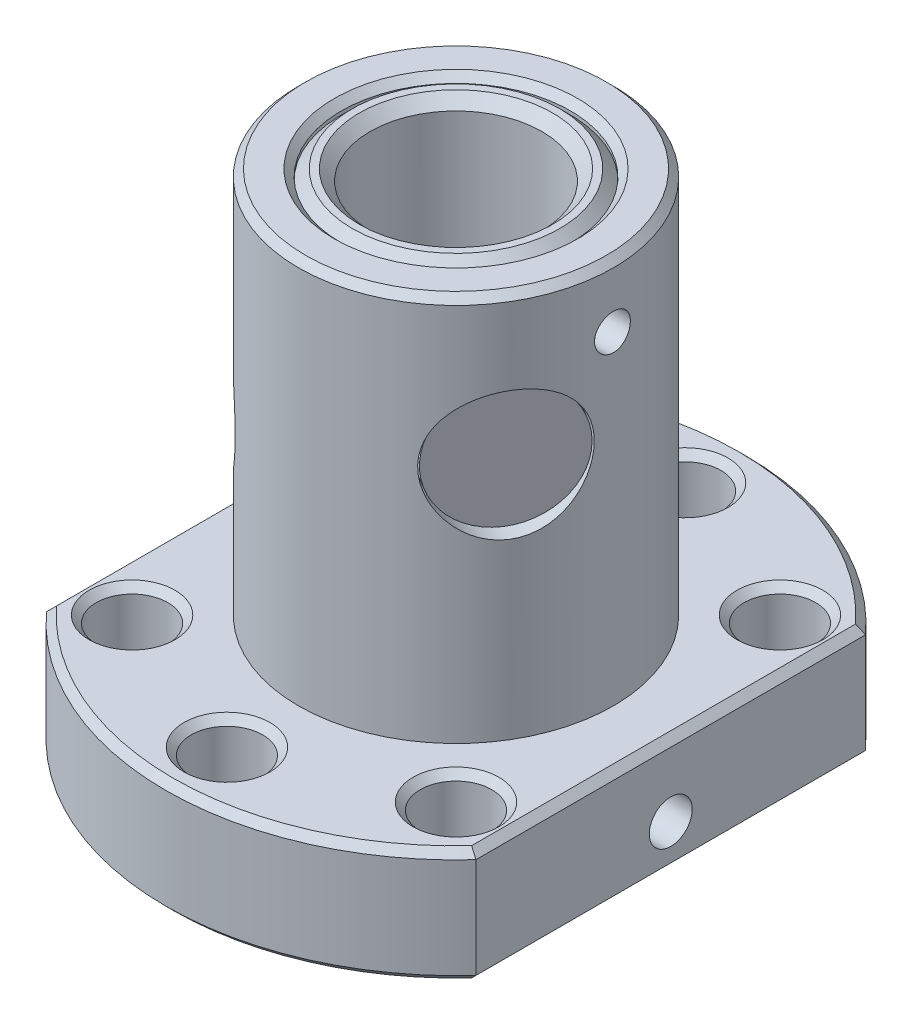
SolidWorks part; units mm, degrees
ref_plane "Front" through (0, 0, 0) normal (0, 0, 1) x (1, 0, 0)
ref_plane "Top" through (0, 0, 0) normal (0, 1, 0) x (1, 0, 0)
ref_plane "Right" through (0, 0, 0) normal (1, 0, 0) x (0, 0, -1)
sketch "Sketch1" plane through (0, 0, 0) normal (0, 1, 0) x (1, 0, 0)
  line L0 (0, 20.25) -> (0, -20.25) construction
  line L1 (-15, 0) -> (15, 0) construction
  line L2 (-15, 13.6038) -> (-15, -13.6038)
  line L3 (15, 13.6038) -> (15, -13.6038)
  arc A0 (-15, -13.6038) -> (15, -13.6038) centre (0, 0) ccw
  arc A1 (15, 13.6038) -> (-15, 13.6038) centre (0, 0) ccw
  dimension "D1" = 40.5
  dimension "D2" = 30
extrude "Boss-Extrude1" add sketch "Sketch1" along normal blind 8
sketch "Sketch2" plane through (0, 8, 0) normal (0, 1, 0) x (1, 0, 0)
  circle A0 centre (0, 0) radius 11
  dimension "D1" = 22
extrude "Boss-Extrude2" add sketch "Sketch2" along normal blind 27
hole_wizard "Ø16.0mm Dowel Hole1" positions "Sketch4" profile "Sketch5" hole size "Ø16.0" standard "ISO" end condition through all
sketch "Sketch4" plane through (0, 0, 0) normal (0, -1, 0) x (-1, 0, 0)
  point P0 (0, 0)
sketch "Sketch5" plane through (0, 0, 0) normal (1, 0, 0) x (0, 0, -1)
  line L0 (0, 0) -> (0, 35)
  line L1 (0, 35) -> (8, 35)
  line L2 (8, 35) -> (8, 0)
  line L5 (8, 0) -> (0, 0)
  line L11 (0, -6.35) -> (0, 107.95) construction
  dimension "Thru Hole Dia." = 16
  dimension "Thru Hole Depth" = 35
hole_wizard "Ø5.0mm Dowel Hole1" positions "Sketch7" profile "Sketch6" hole size "Ø5.0" standard "ISO" end condition up to next
sketch "Sketch7" plane through (0, 0, 0) normal (0, -1, 0) x (-1, 0, 0)
  line L0 (0, -20.25) -> (0, 20.25) construction
  line L2 (15, 0) -> (-15, 0) construction
  line L3 (15, 13.6038) -> (15, -13.6038) construction
  line L4 (-15, -13.6038) -> (-15, 13.6038) construction
  line L6 (0, 0) -> (11.3137, -11.3137) construction
  arc A0 (-15, -13.6038) -> (15, -13.6038) centre (0, 0) ccw construction
  arc A1 (15, 13.6038) -> (-15, 13.6038) centre (0, 0) ccw construction
  point P0 (0, -16)
  point P2 (11.3137, -11.3137)
  point P30 (-11.3137, -11.3137)
  point P32 (-11.3137, 11.3137)
  point P33 (0, 16)
  point P34 (11.3137, 11.3137)
  dimension "D1" = 16
  dimension "D2" = 45
  dimension "D3" = 16
sketch "Sketch6" plane through (0, 0, 16) normal (1, 0, 0) x (0, 0, -1)
  line L0 (0, 0) -> (0, 8)
  line L1 (0, 8) -> (2.5, 8)
  line L2 (2.5, 8) -> (2.5, 0)
  line L5 (2.5, 0) -> (0, 0)
  line L11 (0, -6.35) -> (0, 107.95) construction
  dimension "Thru Hole Dia." = 5
  dimension "Thru Hole Depth" = 8
hole_wizard "Ø3.0mm Dowel Hole1" positions "Sketch9" profile "Sketch8" hole size "Ø3.0" standard "ISO" end condition through all
sketch "Sketch9" plane through (15, 0, 0) normal (1, 0, 0) x (0, 0, -1)
  point P0 (0, 3)
  dimension "D1" = 3
sketch "Sketch8" plane through (15, 3, 0) normal (0, 1, 0) x (0, 0, -1)
  line L0 (0, 0) -> (0, 30)
  line L1 (0, 30) -> (1.5, 30)
  line L2 (1.5, 30) -> (1.5, 0)
  line L5 (1.5, 0) -> (0, 0)
  line L11 (0, -6.35) -> (0, 107.95) construction
  dimension "Thru Hole Dia." = 3
  dimension "Thru Hole Depth" = 30
hole_wizard "M5 Tapped Hole1" positions "3DSketch1" profile "Sketch10" tap size "M5" standard "ISO" end condition up to next
sketch3d "3DSketch1"
  line L1 (0, 0, 0) -> (0, 0, -16) construction
  line L2 (0, 8, -16) -> (0, 0, -16) construction
  line L4 (0, 0, 0) -> (7.7493, 0, -18.7086) construction
  arc A0 (15, 0, -13.6038) -> (-15, 0, -13.6038) centre (0, 0, 0) ccw construction
  point P17 (0, 20.25, 0)
  point P40 (7.7491, 5, -18.7087)
  dimension "D1" = 22.5
  dimension "D2" = 5
sketch "Sketch10" plane through (7.7491, 5, -18.7087) normal (0, 1, 0) x (-0.9239, 0, -0.3827)
  line L0 (0, 0) -> (0, 12.25)
  line L1 (0, 12.25) -> (2.1, 12.25)
  line L2 (2.1, 12.25) -> (2.1, 0)
  line L5 (2.1, 0) -> (0, 0)
  line L11 (0, -6.35) -> (0, 16.6804) construction
  dimension "Thru Tap Drill Dia." = 4.2
  dimension "Thru Tap Drill Depth" = 12.25
cosmetic thread "Hole Thread1" parameters "D1"=6, "D2"=5
hole_wizard "Ø8.0mm Dowel Hole1" positions "3DSketch2" profile "Sketch16" hole size "Ø8.0" standard "ISO" end condition up to next
sketch3d "3DSketch2"
  point P10 (-9.6802, 19.8908, 5.2243)
  point P18 (9.4508, 24.6248, 5.6287)
  point P21 (1.1665, 15, -10.938)
  dimension "D1" = 7
sketch "Sketch16" plane through (-9.6802, 19.8908, 5.2243) normal (0, 1, 0) x (0.4749, 0, 0.88)
  line L0 (0, 0) -> (0, 3)
  line L1 (0, 3) -> (4.5, 3)
  line L2 (4.5, 3) -> (4.5, 0)
  line L5 (4.5, 0) -> (0, 0)
  line L11 (0, -6.35) -> (0, 107.95) construction
  dimension "Thru Hole Dia." = 9
  dimension "Thru Hole Depth" = 3
hole_wizard "M3 Tapped Hole1" positions "Sketch18" profile "Sketch19" tap size "M3" standard "ISO" end condition through all
sketch "Sketch18" plane through (-15, 0, 0) normal (1, 0, 0) x (0, 0, -1)
  point P0 (0, 30.6226)
sketch "Sketch19" plane through (-15, 30.6226, 0) normal (0, 1, 0) x (0, 0, 1)
  line L0 (0, 0) -> (0, 30)
  line L1 (0, 30) -> (1.25, 30)
  line L2 (1.25, 30) -> (1.25, 0)
  line L5 (1.25, 0) -> (0, 0)
  line L11 (0, -6.35) -> (0, 107.95) construction
  dimension "Thru Tap Drill Dia." = 2.5
  dimension "Thru Tap Drill Depth" = 30
cosmetic thread "Hole Thread3" parameters "D2"=3
sketch "Sketch20" plane through (0, 0, 0) normal (0, -1, 0) x (1, 0, 0)
  circle A0 centre (0, 0) radius 8
  circle A1 centre (0, 0) radius 6
  dimension "D1" = 16
  dimension "D2" = 12
extrude "Boss-Extrude3" add sketch "Sketch20" against normal up to surface (35 mm away) separate body up to face at (0, 35, -8)
chamfer "Chamfer1" distance 0.5 23 edges at (0, 35, 11) (0, 35, -8) (15, 8, 0) (0, 8, 20.25) (-15, 8, 0) (0, 8, -20.25) (-11.3137, 8, -8.8137) (0, 8, -13.5) (11.3137, 8, -8.8137) (11.3137, 8, 13.8137) (-11.3137, 8, 13.8137) (0, 8, 18.5) (-11.3137, 0, 8.8137) (11.3137, 0, 8.8137) (11.3137, 0, -13.8137) (0, 0, -18.5) (-11.3137, 0, -13.8137) (0, 0, -8) (-15, 0, 0) (0, 0, 20.25) (15, 0, 0) (0, 0, -20.25) (0, 0, 13.5)
chamfer "Chamfer2" distance 0.75 4 edges at (0, 35, 6) (0, 35, 8) (0, 0, -8) (0, 0, -6)
ref_plane "Plane1" through (0.8483, 0, -7.9549) normal (0.106, 0, -0.9944) x (-0.9944, 0, -0.106)
sketch "Sketch21" plane through (0.8483, 0, -7.9549) normal (0.106, 0, -0.9944) x (-0.9944, 0, -0.106)
  circle A0 centre (0, 15) radius 4.4
  dimension "D1" = 8.8
extrude "Boss-Extrude4" add sketch "Sketch21" along normal blind 2 separate body
ref_plane "Plane2" through (-7.0402, 0, 3.7995) normal (-0.88, 0, 0.4749) x (0.4749, 0, 0.88)
sketch "Sketch22" plane through (-7.0402, 0, 3.7995) normal (-0.88, 0, 0.4749) x (0.4749, 0, 0.88)
  circle A0 centre (0, 19.8908) radius 4.4
  dimension "D1" = 8.8
extrude "Boss-Extrude5" add sketch "Sketch22" along normal blind 2
ref_plane "Plane3" through (6.8733, 0, 4.0936) normal (0.8592, 0, 0.5117) x (0.5117, 0, -0.8592)
sketch "Sketch23" plane through (6.8733, 0, 4.0936) normal (0.8592, 0, 0.5117) x (0.5117, 0, -0.8592)
  circle A0 centre (0, 24.6248) radius 4.4
  dimension "D1" = 8.8
extrude "Boss-Extrude6" add sketch "Sketch23" along normal blind 2 separate body
